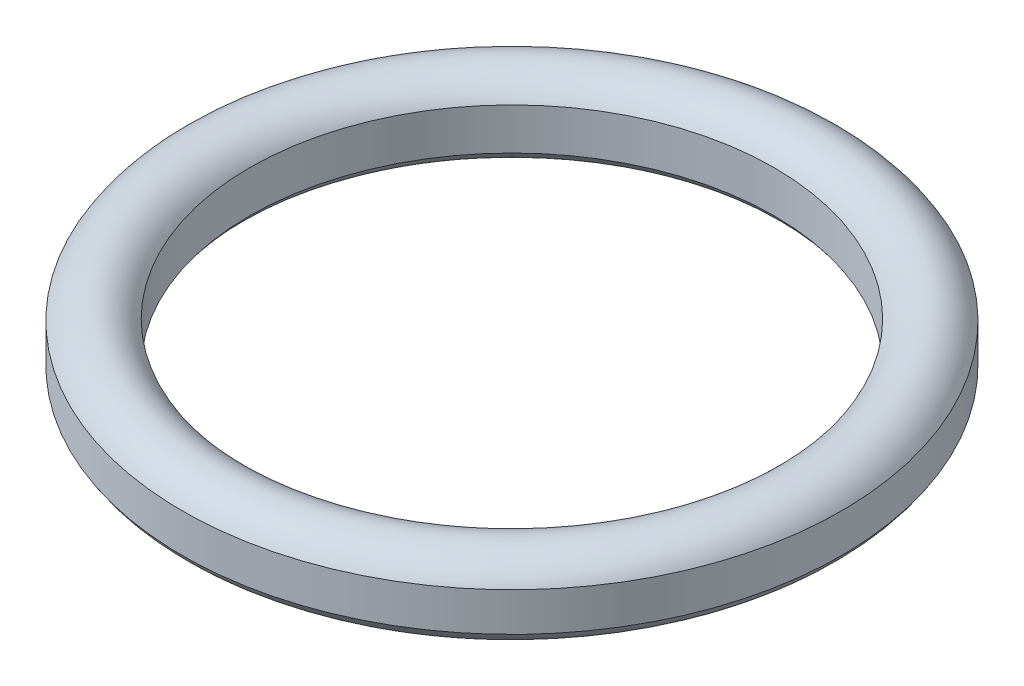
SolidWorks part; units mm, degrees
material "Plain Carbon Steel"
ref_plane "Piano frontale" through (0, 0, 0) normal (0, 0, 1) x (1, 0, 0)
ref_plane "Piano superiore" through (0, 0, 0) normal (0, 1, 0) x (1, 0, 0)
ref_plane "Piano destro" through (0, 0, 0) normal (1, 0, 0) x (0, 0, -1)
sketch "Schizzo1" plane through (0, 0, 0) normal (0, 0, 1) x (1, 0, 0)
  line L0 (-9.86, 0) -> (0, 0) construction
  line L1 (0, 0) -> (0, 8.7785) construction
  line L2 (-8.75, -0.6957) -> (-8.75, 0.6957)
  line L3 (-11, -0.6454) -> (-11, 0.6454)
  circle A0 centre (-9.86, 0) radius 1.31
  dimension "D2" = 2.62
  dimension "D1" = 19.72
  dimension "D3" = 22
  dimension "D4" = 17.5
revolve "Rivoluzione1" add sketch "Schizzo1" angle 360 about L1 region at (-9.869, 0, 0)
